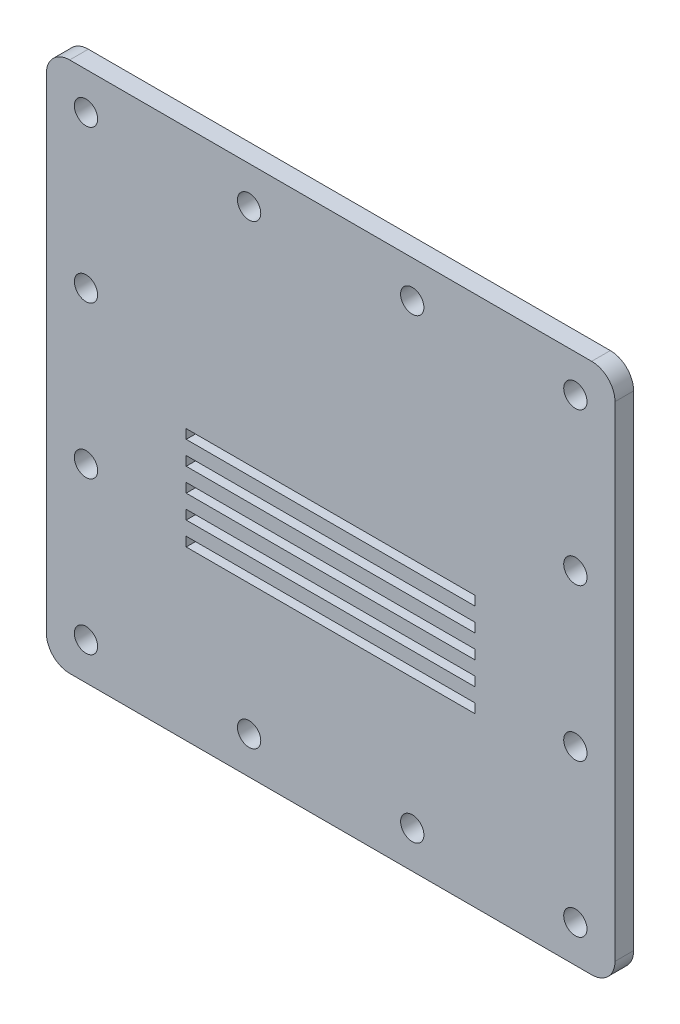
SolidWorks part; units mm, degrees
ref_plane "Front Plane" through (0, 0, 0) normal (0, 0, 1) x (1, 0, 0)
ref_plane "Top Plane" through (0, 0, 0) normal (0, 1, 0) x (1, 0, 0)
ref_plane "Right Plane" through (0, 0, 0) normal (1, 0, 0) x (0, 0, -1)
sketch "Sketch1" plane through (0, 0, 0) normal (0, 0, 1) x (1, 0, 0)
  line L1 (-21.5, -19.5) -> (21.5, -19.5) construction
  line L2 (-21.5, -19.5) -> (-21.5, 19.5) construction
  line L3 (-21.5, 19.5) -> (21.5, 19.5) construction
  line L4 (21.5, -19.5) -> (21.5, 19.5) construction
  line L5 (-21.5, -19.5) -> (21.5, 19.5) construction
  line L6 (-21.5, 19.5) -> (21.5, -19.5) construction
  line L7 (-30.5, -28.5) -> (30.5, -28.5)
  line L8 (-30.5, -28.5) -> (-30.5, 28.5)
  line L9 (-30.5, 28.5) -> (30.5, 28.5)
  line L10 (30.5, -28.5) -> (30.5, 28.5)
  line L11 (-30.5, -28.5) -> (30.5, 28.5) construction
  line L12 (-30.5, 28.5) -> (30.5, -28.5) construction
  point P0 (0, 0)
  point P6 (0, 0)
  dimension "D1" = 43
  dimension "D2" = 39
  dimension "D3" = 9
  dimension "D4" = 9
extrude "Boss-Extrude1" add sketch "Sketch1" along normal blind 2
fillet "Fillet1" radius 2.5 4 edges at (-30.5, -28.5, 1) (30.5, -28.5, 1) (-30.5, 28.5, 1) (30.5, 28.5, 1)
sketch "Sketch2" plane through (0, 0, 2) normal (0, 0, 1) x (1, 0, 0)
  line L0 (-21.5, -19.5) -> (-21.5, 19.5) construction
  line L1 (-26.25, -24.5) -> (26.25, -24.5) construction
  line L2 (-26.25, -24.5) -> (-26.25, 24.5) construction
  line L3 (-26.25, 24.5) -> (26.25, 24.5) construction
  line L4 (26.25, -24.5) -> (26.25, 24.5) construction
  line L5 (-26.25, -24.5) -> (26.25, 24.5) construction
  line L6 (-26.25, 24.5) -> (26.25, -24.5) construction
  line L7 (-21.5, 19.5) -> (21.5, 19.5) construction
  circle A0 centre (-26.25, 24.5) radius 1.25
  circle A1 centre (-8.75, 24.5) radius 1.25
  circle A2 centre (8.75, 24.5) radius 1.25
  circle A3 centre (26.25, 24.5) radius 1.25
  circle A6 centre (26.25, 8.1667) radius 1.25
  circle A9 centre (26.25, -8.1667) radius 1.25
  circle A10 centre (-8.75, -24.5) radius 1.25
  circle A11 centre (8.75, -24.5) radius 1.25
  circle A12 centre (26.25, -24.5) radius 1.25
  circle A13 centre (-26.25, 8.1667) radius 1.25
  circle A14 centre (-26.25, -8.1667) radius 1.25
  circle A15 centre (-26.25, -24.5) radius 1.25
  circle A16 centre (-8.75, 8.1667) radius 1.25 [skipped]
  circle A17 centre (8.75, 8.1667) radius 1.25 [skipped]
  circle A18 centre (8.75, -8.1667) radius 1.25 [skipped]
  circle A19 centre (-8.75, -8.1667) radius 1.25 [skipped]
  point P0 (0, 0)
  dimension "D3" = 2.5
  dimension "D1" = 4.75
  dimension "D2" = 5
  dimension "D5" = 4
  dimension "D4" = 4
extrude "Cut-Extrude1" cut sketch "Sketch2" against normal up to surface (2 mm away) up to face at (0, 0, 0)
sketch "Sketch3" plane through (0, 0, 2) normal (0, 0, 1) x (1, 0, 0)
  line L0 (-30.5, -28.5) -> (-30.5, 28.5) construction
  line L1 (-15.5, 0.5) -> (15.5, 0.5)
  line L2 (-15.5, 0.5) -> (-15.5, -0.5)
  line L3 (-15.5, -0.5) -> (15.5, -0.5)
  line L4 (15.5, 0.5) -> (15.5, -0.5)
  line L5 (-15.5, 0.5) -> (15.5, -0.5) construction
  line L6 (-15.5, -0.5) -> (15.5, 0.5) construction
  line L7 (-15.5, -2) -> (-15.5, -3)
  line L8 (-15.5, -2) -> (15.5, -2)
  line L9 (15.5, -2) -> (15.5, -3)
  line L10 (-15.5, -3) -> (15.5, -3)
  line L11 (-15.5, -4.5) -> (-15.5, -5.5)
  line L12 (-15.5, -4.5) -> (15.5, -4.5)
  line L13 (15.5, -4.5) -> (15.5, -5.5)
  line L14 (-15.5, -5.5) -> (15.5, -5.5)
  line L15 (-15.5, -7) -> (-15.5, -8)
  line L16 (-15.5, -7) -> (15.5, -7)
  line L17 (15.5, -7) -> (15.5, -8)
  line L18 (-15.5, -8) -> (15.5, -8)
  line L19 (-15.5, -9.5) -> (-15.5, -10.5)
  line L20 (-15.5, -9.5) -> (15.5, -9.5)
  line L21 (15.5, -9.5) -> (15.5, -10.5)
  line L22 (-15.5, -10.5) -> (15.5, -10.5)
  point P0 (0, 0)
  dimension "D1" = 1
  dimension "D2" = 15
  dimension "D4" = 2.5
  dimension "D3" = 5
extrude "Cut-Extrude2" cut sketch "Sketch3" against normal up to surface (2 mm away) up to face at (-27.5, -24.5, 0)
equation "\"case_width\"=43.00"
equation "\"D1@Sketch1\"=\"case_width\""
